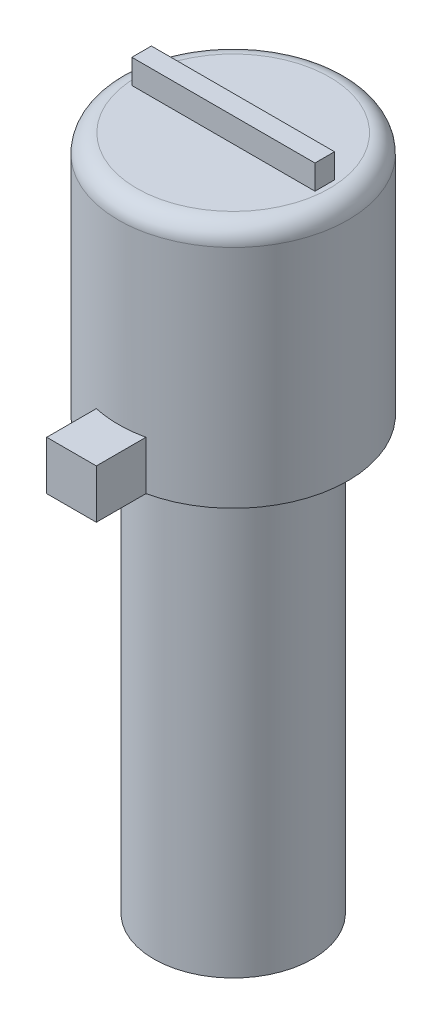
SolidWorks part; units mm, degrees
ref_plane "Front Plane" through (0, 0, 0) normal (0, 0, 1) x (1, 0, 0)
ref_plane "Top Plane" through (0, 0, 0) normal (0, 1, 0) x (1, 0, 0)
ref_plane "Right Plane" through (0, 0, 0) normal (1, 0, 0) x (0, 0, -1)
sketch "Sketch1" plane through (0, 0, 0) normal (0, 1, 0) x (1, 0, 0)
  circle A0 centre (0, 0) radius 3.25
  dimension "D1" = 6.5
extrude "Boss-Extrude1" add sketch "Sketch1" along normal blind 17.686 contours A0
sketch "Sketch2" plane through (0, 0, 0) normal (0, -1, 0) x (1, 0, 0)
  circle A1 centre (0, 0) radius 1.75
  dimension "D1" = 3.5
extrude "Cut-Extrude1" [suppressed] cut sketch "Sketch2" against normal blind 2.5
sketch "Sketch6" plane through (0, 17.686, 0) normal (0, 1, 0) x (1, 0, 0)
  circle A0 centre (0, 0) radius 4.7
  dimension "D1" = 9.4
extrude "Boss-Extrude2" add sketch "Sketch6" along normal blind 10 contours A0
sketch "Sketch7" plane through (0, 27.686, 0) normal (0, 1, 0) x (1, 0, 0)
  line L1 (-0.4, -3.75) -> (0.4, -3.75)
  line L2 (-0.4, -3.75) -> (-0.4, 3.75)
  line L3 (-0.4, 3.75) -> (0.4, 3.75)
  line L4 (0.4, -3.75) -> (0.4, 3.75)
  line L5 (-0.4, -3.75) -> (0.4, 3.75) construction
  line L6 (-0.4, 3.75) -> (0.4, -3.75) construction
  line L7 (-3.75, -0.4) -> (3.75, -0.4)
  line L8 (-3.75, -0.4) -> (-3.75, 0.4)
  line L9 (-3.75, 0.4) -> (3.75, 0.4)
  line L10 (3.75, -0.4) -> (3.75, 0.4)
  line L11 (-3.75, -0.4) -> (3.75, 0.4) construction
  line L12 (-3.75, 0.4) -> (3.75, -0.4) construction
  point P0 (0, 0)
  point P6 (0, 0)
  dimension "D1" = 0.8
  dimension "D2" = 7.5
  dimension "D3" = 7.5
  dimension "D4" = 0.8
sketch "Sketch8" plane through (0, 27.686, 0) normal (0, 1, 0) x (1, 0, 0)
  line L0 (0.4, 3.75) -> (-0.4, 3.75)
  line L1 (-0.4, 3.75) -> (-0.4, 0.4)
  line L2 (-0.4, -3.75) -> (-0.4, 3.75) construction
  line L3 (-3.75, 0.4) -> (3.75, 0.4) construction
  line L4 (-0.4, 0.4) -> (-3.75, 0.4)
  line L5 (-3.75, 0.4) -> (-3.75, -0.4)
  line L6 (-3.75, -0.4) -> (-0.4, -0.4)
  line L7 (-3.75, -0.4) -> (3.75, -0.4) construction
  line L8 (-0.4, -0.4) -> (-0.4, -3.75)
  line L9 (-0.4, -3.75) -> (0.4, -3.75)
  line L10 (0.4, -3.75) -> (0.4, -0.4)
  line L11 (0.4, -3.75) -> (0.4, 3.75) construction
  line L12 (0.4, -0.4) -> (3.75, -0.4)
  line L13 (3.75, -0.4) -> (3.75, 0.4)
  line L14 (3.75, 0.4) -> (0.4, 0.4)
  line L15 (0.4, 0.4) -> (0.4, 3.75)
extrude "Boss-Extrude3" add sketch "Sketch8" along normal blind 1
fillet "Fillet1" radius 0.75 1 edges at (0, 27.686, 4.7)
sketch "Sketch9" plane through (0, 27.686, 0) normal (0, 1, 0) x (1, 0, 0)
  line L1 (-0.4, 3.75) -> (0.4, 3.75)
  line L2 (-0.4, 3.75) -> (-0.4, 0.4)
  line L3 (-0.4, 0.4) -> (0.4, 0.4)
  line L4 (0.4, 3.75) -> (0.4, 0.4)
  line L5 (-0.4, -0.4) -> (0.4, -0.4)
  line L6 (-0.4, -0.4) -> (-0.4, -3.75)
  line L7 (-0.4, -3.75) -> (0.4, -3.75)
  line L8 (0.4, -0.4) -> (0.4, -3.75)
extrude "Cut-Extrude3" cut sketch "Sketch9" along normal up to surface (1 mm away) up to face at (0, 28.686, 0)
sketch "Sketch10" plane through (0, 17.686, 0) normal (0, -1, 0) x (1, 0, 0)
  line L0 (0, 4.7) -> (0, -4.7) construction
  line L1 (-1.016, 4.5889) -> (-1.016, 6.6209)
  line L2 (-1.016, 6.6209) -> (1.016, 6.6209)
  line L3 (1.016, 6.6209) -> (1.016, 4.5889)
  circle A0 centre (0, 0) radius 4.7 construction
  circle A2 centre (0, 0) radius 4.7
  circle A3 centre (0, 0) radius 4.7
  circle M5 centre (0, 0) radius 4.7
  dimension "D1" = 0
  dimension "D2" = 2.032
  dimension "D3" = 2.032
extrude "Boss-Extrude4" add sketch "Sketch10" against normal blind 2 contours L3 L2 L1 A3 M5 region at (0, 17.686, 5.6417)
